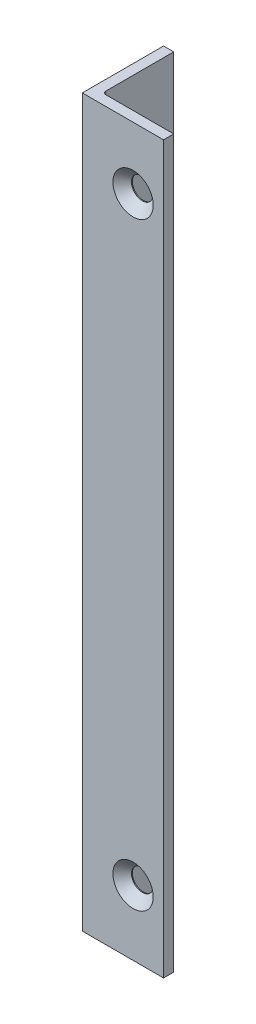
SolidWorks part; units mm, degrees
material "6061-T6 (SS)"
ref_plane "Front Plane" through (0, 0, 0) normal (0, 0, 1) x (1, 0, 0)
ref_plane "Top Plane" through (0, 0, 0) normal (0, 1, 0) x (1, 0, 0)
ref_plane "Right Plane" through (0, 0, 0) normal (1, 0, 0) x (0, 0, -1)
sketch "Sketch1" plane through (0, 0, 0) normal (0, 1, 0) x (1, 0, 0)
  line L1 (-6.35, -6.35) -> (6.35, -6.35)
  line L2 (-6.35, -6.35) -> (-6.35, 6.35)
  line L3 (-6.35, 6.35) -> (6.35, 6.35)
  line L4 (6.35, -6.35) -> (6.35, 6.35)
  line L5 (-6.35, -6.35) -> (6.35, 6.35) construction
  line L6 (-6.35, 6.35) -> (6.35, -6.35) construction
  point P0 (0, 0)
  dimension "D1" = 12.7
  dimension "D2" = 12.7
extrude "Boss-Extrude1" add sketch "Sketch1" along normal mid plane 113.5
sketch "Sketch2" plane through (0, 56.75, 0) normal (0, 1, 0) x (1, 0, 0)
  line L0 (-6.35, 6.35) -> (-6.35, -6.35) construction
  line L1 (6.35, 6.35) -> (-4.7625, 6.35)
  line L2 (6.35, 6.35) -> (6.35, -4.7625)
  line L3 (6.35, -4.7625) -> (-4.7625, -4.7625)
  line L4 (-4.7625, 6.35) -> (-4.7625, -4.7625)
  line L5 (-6.35, -6.35) -> (6.35, -6.35) construction
  dimension "D1" = 1.5875
  dimension "D2" = 1.5875
extrude "Cut-Extrude1" cut sketch "Sketch2" against normal through all
fillet "Fillet1" radius 0.508 1 edges at (-4.7625, 0, 4.7625)
hole_wizard "CSK for M3 Flat Head Machine Screw1" positions "Sketch3" profile "Sketch4" countersink size "M3" standard "ANSI Metric" end condition through all
sketch "Sketch3" plane through (0, 0, 6.35) normal (0, 0, 1) x (1, 0, 0)
  line L0 (-4.7625, -56.75) -> (-4.7625, 56.75) construction
  line L1 (-6.35, 56.75) -> (6.35, 56.75) construction
  point P0 (1.5875, 47.075)
  dimension "D1" = 6.35
  dimension "D2" = 9.675
sketch "Sketch4" plane through (1.5875, 47.075, 6.35) normal (1, 0, 0) x (0, -1, 0)
  line L0 (0, 0) -> (0, 12.7)
  line L1 (0, 12.7) -> (1.7, 12.7)
  line L2 (1.7, 12.7) -> (1.7, 1.45)
  line L3 (1.7, 1.45) -> (3.15, 0)
  line L5 (3.15, 0) -> (0, 0)
  line L6 (-1.7, 1.45) -> (-3.15, 0) construction
  line L11 (0, -6.35) -> (0, 107.95) construction
  dimension "Thru Hole Dia." = 3.4
  dimension "Thru Hole Depth" = 12.7
  dimension "Near C'Sink Dia." = 6.3
  dimension "Near C'Sink Angle" = 90
hole_wizard "CSK for M3 Flat Head Machine Screw2" positions "Sketch5" profile "Sketch6" countersink size "M3" standard "ANSI Metric" end condition through all
sketch "Sketch5" plane through (-6.35, 0, 0) normal (-1, 0, 0) x (0, 0, 1)
  line L0 (4.7625, -56.75) -> (4.7625, 56.75) construction
  line L1 (-6.35, 56.75) -> (6.35, 56.75) construction
  point P0 (-1.5875, 47.075)
  dimension "D1" = 6.35
  dimension "D2" = 9.675
sketch "Sketch6" plane through (-6.35, 47.075, -1.5875) normal (0, 1, 0) x (0, 0, 1)
  line L0 (0, 0) -> (0, 12.7)
  line L1 (0, 12.7) -> (1.7, 12.7)
  line L2 (1.7, 12.7) -> (1.7, 1.45)
  line L3 (1.7, 1.45) -> (3.15, 0)
  line L5 (3.15, 0) -> (0, 0)
  line L6 (-1.7, 1.45) -> (-3.15, 0) construction
  line L11 (0, -6.35) -> (0, 107.95) construction
  dimension "Thru Hole Dia." = 3.4
  dimension "Thru Hole Depth" = 12.7
  dimension "Near C'Sink Dia." = 6.3
  dimension "Near C'Sink Angle" = 90
hole_wizard "CSK for M3 Flat Head Machine Screw3" positions "Sketch7" profile "Sketch8" countersink size "M3" standard "ANSI Metric" end condition through all
sketch "Sketch7" plane through (0, 0, 6.35) normal (0, 0, 1) x (1, 0, 0)
  line L1 (-4.7625, -56.75) -> (-4.7625, 56.75) construction
  line L2 (-6.35, -56.75) -> (6.35, -56.75) construction
  point P0 (1.5875, -46.575)
  dimension "D1" = 6.35
  dimension "D2" = 10.175
sketch "Sketch8" plane through (1.5875, -46.575, 6.35) normal (1, 0, 0) x (0, -1, 0)
  line L0 (0, 0) -> (0, 12.7)
  line L1 (0, 12.7) -> (1.7, 12.7)
  line L2 (1.7, 12.7) -> (1.7, 1.45)
  line L3 (1.7, 1.45) -> (3.15, 0)
  line L5 (3.15, 0) -> (0, 0)
  line L6 (-1.7, 1.45) -> (-3.15, 0) construction
  line L11 (0, -6.35) -> (0, 107.95) construction
  dimension "Thru Hole Dia." = 3.4
  dimension "Thru Hole Depth" = 12.7
  dimension "Near C'Sink Dia." = 6.3
  dimension "Near C'Sink Angle" = 90
hole_wizard "CSK for M3 Flat Head Machine Screw4" positions "Sketch9" profile "Sketch10" countersink size "M3" standard "ANSI Metric" end condition through all
sketch "Sketch9" plane through (-6.35, 0, 0) normal (-1, 0, 0) x (0, 0, 1)
  line L0 (4.7625, -56.75) -> (4.7625, 56.75) construction
  line L1 (-6.35, -56.75) -> (6.35, -56.75) construction
  point P0 (-1.5875, -46.575)
  point P10 (-1.5875, -46.3471)
  dimension "D1" = 6.35
  dimension "D2" = 10.175
sketch "Sketch10" plane through (-6.35, -46.575, -1.5875) normal (0, 1, 0) x (0, 0, 1)
  line L0 (0, 0) -> (0, 12.7)
  line L1 (0, 12.7) -> (1.7, 12.7)
  line L2 (1.7, 12.7) -> (1.7, 1.45)
  line L3 (1.7, 1.45) -> (3.15, 0)
  line L5 (3.15, 0) -> (0, 0)
  line L6 (-1.7, 1.45) -> (-3.15, 0) construction
  line L11 (0, -6.35) -> (0, 107.95) construction
  dimension "Thru Hole Dia." = 3.4
  dimension "Thru Hole Depth" = 12.7
  dimension "Near C'Sink Dia." = 6.3
  dimension "Near C'Sink Angle" = 90
